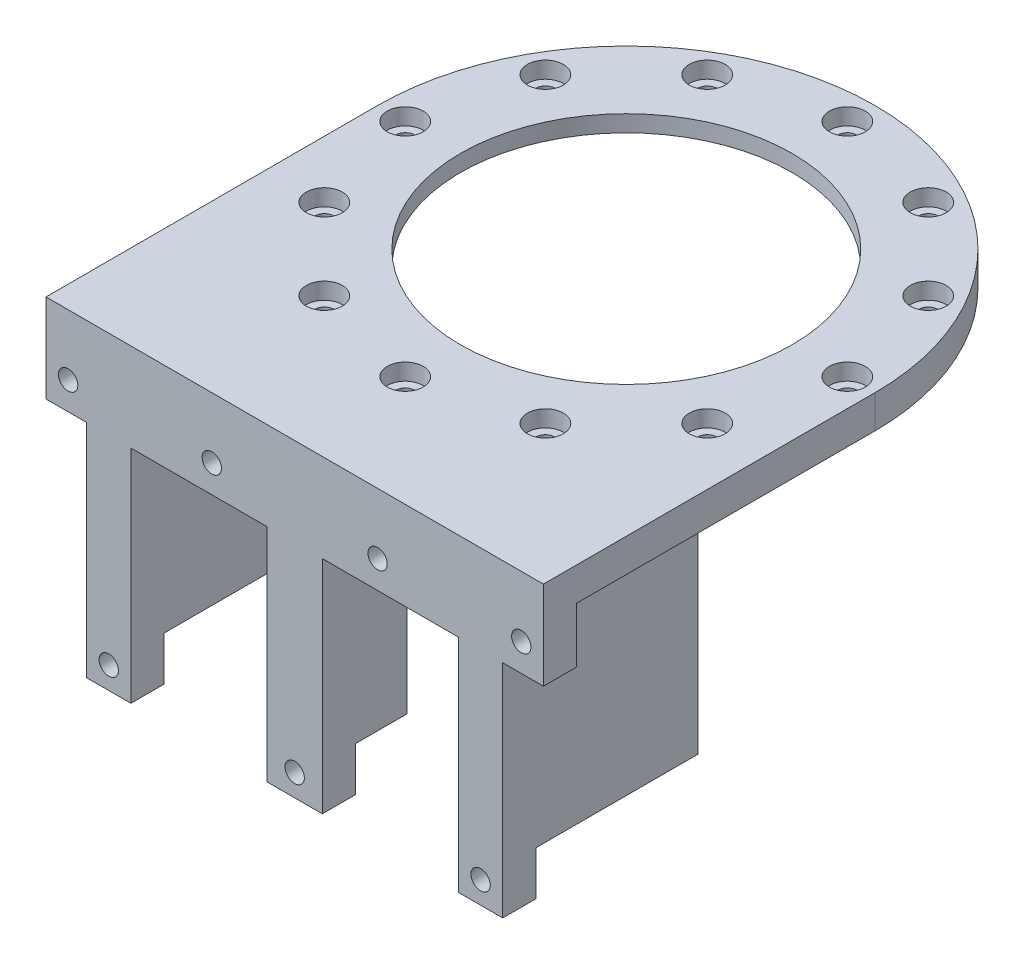
SolidWorks part; units mm, degrees
ref_plane "Front Plane" through (0, 0, 0) normal (0, 0, 1) x (1, 0, 0)
ref_plane "Top Plane" through (0, 0, 0) normal (0, 1, 0) x (1, 0, 0)
ref_plane "Right Plane" through (0, 0, 0) normal (1, 0, 0) x (0, 0, -1)
sketch "Sketch1" plane through (0, 0, 0) normal (0, 1, 0) x (1, 0, 0)
  line L0 (0, 0) -> (0, 52.0165) construction
  circle A0 centre (0, 0) radius 45
  circle A1 centre (0, 0) radius 30
  circle A2 centre (0, 0) radius 40 construction
  circle A3 centre (0, 40) radius 1.75
  circle A4 centre (0, 0) radius 36 construction
  circle A5 centre (20, 34.641) radius 1.75
  circle A6 centre (34.641, 20) radius 1.75
  circle A7 centre (40, 0) radius 1.75
  circle A8 centre (34.641, -20) radius 1.75
  circle A9 centre (20, -34.641) radius 1.75
  circle A10 centre (0, -40) radius 1.75
  circle A11 centre (-20, -34.641) radius 1.75
  circle A12 centre (-34.641, -20) radius 1.75
  circle A13 centre (-40, 0) radius 1.75
  circle A14 centre (-34.641, 20) radius 1.75
  circle A15 centre (-20, 34.641) radius 1.75
  point P21 (0, 0)
  point P34 (0, 0)
  point P48 (0, 0)
  point P72 (0, 0)
  dimension "D1" = 90
  dimension "D2" = 60
  dimension "D4" = 3.5
  dimension "D5" = 72
  dimension "D6" = 12
  dimension "D3" = 80
extrude "Boss-Extrude1" add sketch "Sketch1" along normal blind 6
sketch "Sketch2" plane through (0, 0, 0) normal (0, -1, 0) x (1, 0, 0)
  circle A0 centre (0, 0) radius 36
  dimension "D1" = 72
extrude "Cut-Extrude1" cut sketch "Sketch2" against normal blind 3
sketch "Sketch3" plane through (0, 6, 0) normal (0, 1, 0) x (1, 0, 0)
  line L0 (0, 0) -> (49.8808, 0) construction
  circle A0 centre (40, 0) radius 3.25
  circle A1 centre (34.641, -20) radius 3.25
  circle A2 centre (20, -34.641) radius 3.25
  circle A3 centre (0, -40) radius 3.25
  circle A4 centre (-20, -34.641) radius 3.25
  circle A5 centre (-34.641, -20) radius 3.25
  circle A6 centre (-40, 0) radius 3.25
  circle A7 centre (-34.641, 20) radius 3.25
  circle A8 centre (-20, 34.641) radius 3.25
  circle A9 centre (0, 40) radius 3.25
  circle A10 centre (20, 34.641) radius 3.25
  circle A11 centre (34.641, 20) radius 3.25
  point P30 (0, 0)
  dimension "D1" = 6.5
  dimension "D2" = 12
extrude "Cut-Extrude2" cut sketch "Sketch3" against normal blind 3
sketch "Sketch4" plane through (0, 0, 0) normal (0, -1, 0) x (1, 0, 0)
  line L0 (45, 0) -> (45, 60)
  line L1 (-45, 0) -> (-45, 60)
  line L2 (45, 60) -> (-45, 60)
  line L3 (45, 0) -> (-45, 0) construction
  circle A1 centre (0, 0) radius 45 construction
  arc A2 (45, 0) -> (-45, 0) centre (0, 0) ccw
  dimension "D1" = 60
  dimension "D2" = 90
extrude "Boss-Extrude4" add sketch "Sketch4" against normal blind 6
sketch "Sketch5" plane through (0, 0, 0) normal (0, -1, 0) x (1, 0, 0)
  line L0 (45, 0) -> (45, 60) construction
  line L1 (45, 54) -> (-45, 54)
  line L2 (45, 54) -> (45, 60)
  line L3 (45, 60) -> (-45, 60)
  line L4 (-45, 54) -> (-45, 60)
  dimension "D1" = 6
extrude "Boss-Extrude6" add sketch "Sketch5" along normal blind 10
sketch "Sketch6" plane through (0, 0, 0) normal (0, -1, 0) x (1, 0, 0)
  line L0 (0, 0) -> (0, 68.4249) construction
  line L1 (34.641, 20) -> (34.641, 68.4249) construction
  line L2 (37.641, 24.6608) -> (37.641, 60)
  line L3 (45, 60) -> (-45, 60) construction
  line L4 (37.641, 60) -> (29.641, 60)
  line L5 (29.641, 60) -> (29.641, 33.8587)
  line L6 (-5, 60) -> (5, 60)
  line L7 (5, 60) -> (5, 44.7214)
  line L8 (-5, 60) -> (-5, 44.7214)
  line L9 (-29.641, 60) -> (-29.641, 33.8587)
  line L10 (-37.641, 60) -> (-29.641, 60)
  line L11 (-37.641, 24.6608) -> (-37.641, 60)
  arc A0 (37.641, 24.6608) -> (29.641, 33.8587) centre (0, 0) ccw
  arc A1 (5, 44.7214) -> (-5, 44.7214) centre (0, 0) ccw
  arc A2 (-37.641, 24.6608) -> (-29.641, 33.8587) centre (0, 0) cw
  point P17 (0, 60)
  dimension "D1" = 90
  dimension "D2" = 3
  dimension "D3" = 5
  dimension "D4" = 5
extrude "Boss-Extrude7" add sketch "Sketch6" along normal blind 50
sketch "Sketch7" plane through (37.641, 0, 0) normal (1, 0, 0) x (0, 0, -1)
  line L0 (-24.6608, -42) -> (-54, -42)
  line L1 (-24.6608, -50) -> (-24.6608, 0) construction
  line L2 (-54, -42) -> (-54, -50)
  line L3 (-24.6608, -50) -> (-60, -50) construction
  line L4 (-60, -50) -> (-60, -10) construction
  line L5 (-24.6608, -42) -> (-24.6608, -50)
  line L6 (-24.6608, -50) -> (-54, -50)
  dimension "D1" = 6
  dimension "D2" = 8
extrude "Cut-Extrude3" cut sketch "Sketch7" against normal through all
sketch "Sketch8" plane through (0, 0, 54) normal (0, 0, -1) x (-1, 0, 0)
  line L0 (45, -5) -> (-45, -5) construction
  line L1 (45, -10) -> (45, 0) construction
  line L2 (-45, -10) -> (-45, 0) construction
  line L3 (33.641, -50) -> (33.641, -42) construction
  line L4 (37.641, -50) -> (29.641, -50) construction
  line L5 (37.641, -42) -> (29.641, -42) construction
  line L6 (0, -50) -> (0, -42) construction
  line L7 (5, -50) -> (-5, -50) construction
  line L8 (5, -42) -> (-5, -42) construction
  line L9 (-33.641, -50) -> (-33.641, -42) construction
  line L10 (-29.641, -50) -> (-37.641, -50) construction
  line L11 (-37.641, -42) -> (-29.641, -42) construction
  circle A0 centre (41, -5) radius 1.75
  circle A1 centre (33.641, -46) radius 1.75
  circle A2 centre (0, -46) radius 1.75
  circle A3 centre (15, -5) radius 1.75
  circle A4 centre (-33.641, -46) radius 1.75
  circle A5 centre (-41, -5) radius 1.75
  circle A6 centre (-15, -5) radius 1.75
  point P32 (0, -5)
  dimension "D1" = 3.5
  dimension "D3" = 3.5
  dimension "D5" = 3.5
  dimension "D7" = 3.5
  dimension "D2" = 4
  dimension "D4" = 4
  dimension "D6" = 4
  dimension "D8" = 15
extrude "Cut-Extrude5" cut sketch "Sketch8" against normal through all
sketch "草图1" plane through (0, 0, 54) normal (0, 0, -1) x (-1, 0, 0)
